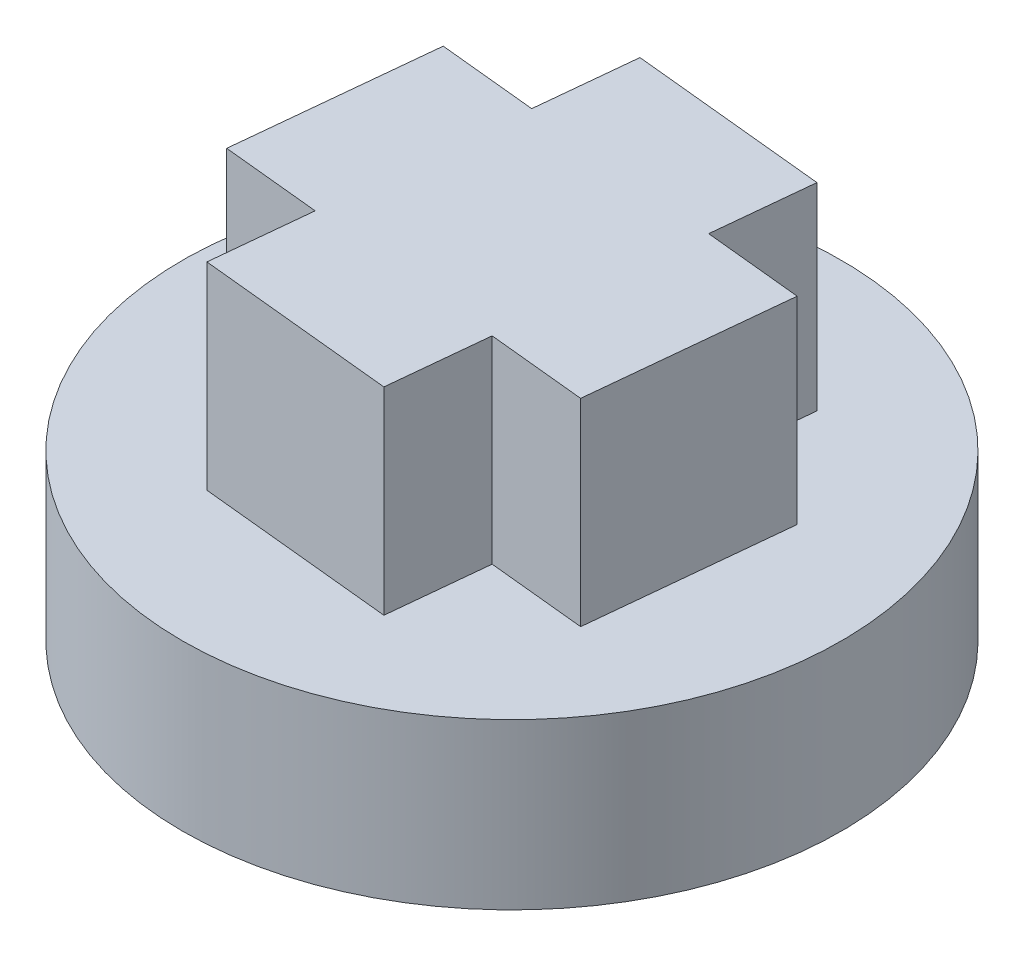
SolidWorks part; units mm, degrees
ref_plane "前视基准面" through (0, 0, 0) normal (0, 0, 1) x (1, 0, 0)
ref_plane "上视基准面" through (0, 0, 0) normal (0, 1, 0) x (1, 0, 0)
ref_plane "右视基准面" through (0, 0, 0) normal (1, 0, 0) x (0, 0, -1)
sketch "草图1" plane through (0, 0, 0) normal (0, 1, 0) x (1, 0, 0)
  line L1 (2.5539, -1.838) -> (2.8687, 1.2927)
  line L2 (2.8687, 1.2927) -> (0.3148, 3.1308)
  line L3 (0.3148, 3.1308) -> (-2.5539, 1.838)
  line L4 (-2.5539, 1.838) -> (-2.8687, -1.2927)
  line L5 (-2.8687, -1.2927) -> (-0.3148, -3.1308)
  line L6 (-0.3148, -3.1308) -> (2.5539, -1.838)
  circle A0 centre (0, 0) radius 5
  circle A1 centre (0, 0) radius 2.725 construction
  dimension "D1" = 10
  dimension "D2" = 5.45
extrude "凸台-拉伸1" add sketch "草图1" along normal blind 2
sketch "草图2" plane through (0, 2, 0) normal (0, 1, 0) x (1, 0, 0)
  line L0 (-2.8349, 1.7926) -> (3.135, 1.1923)
  line L1 (-2.8349, 1.7926) -> (-3.135, -1.1923)
  line L2 (3.135, 1.1923) -> (2.8349, -1.7926)
  line L3 (-3.135, -1.1923) -> (2.8349, -1.7926)
  dimension "D1" = 3
  dimension "D2" = 6
  dimension "D3" = 3
  dimension "D4" = 1.5
extrude "凸台-拉伸2" add sketch "草图2" along normal blind 3.5
sketch "草图3" plane through (0, 2, 0) normal (0, 1, 0) x (1, 0, 0)
  line L2 (-1.1923, 3.135) -> (-1.7926, -2.8349)
  line L3 (-1.1923, 3.135) -> (1.7926, 2.8349)
  line L4 (-1.7926, -2.8349) -> (1.1923, -3.135)
  line L5 (1.7926, 2.8349) -> (1.1923, -3.135)
  line L6 (-3.135, -1.1923) -> (2.8349, -1.7926) construction
  line L7 (2.8349, -1.7926) -> (3.135, 1.1923) construction
  line L8 (-2.8349, 1.7926) -> (-3.135, -1.1923) construction
  dimension "D2" = 1.5
  dimension "D3" = 1.5
  dimension "D4" = 1.5
extrude "凸台-拉伸3" add sketch "草图3" along normal blind 3.5
sketch "草图4" plane through (0, 2, 0) normal (0, 1, 0) x (1, 0, 0)
  circle A0 centre (0, 0) radius 5
extrude "凸台-拉伸4" add sketch "草图4" along normal blind 0.5
